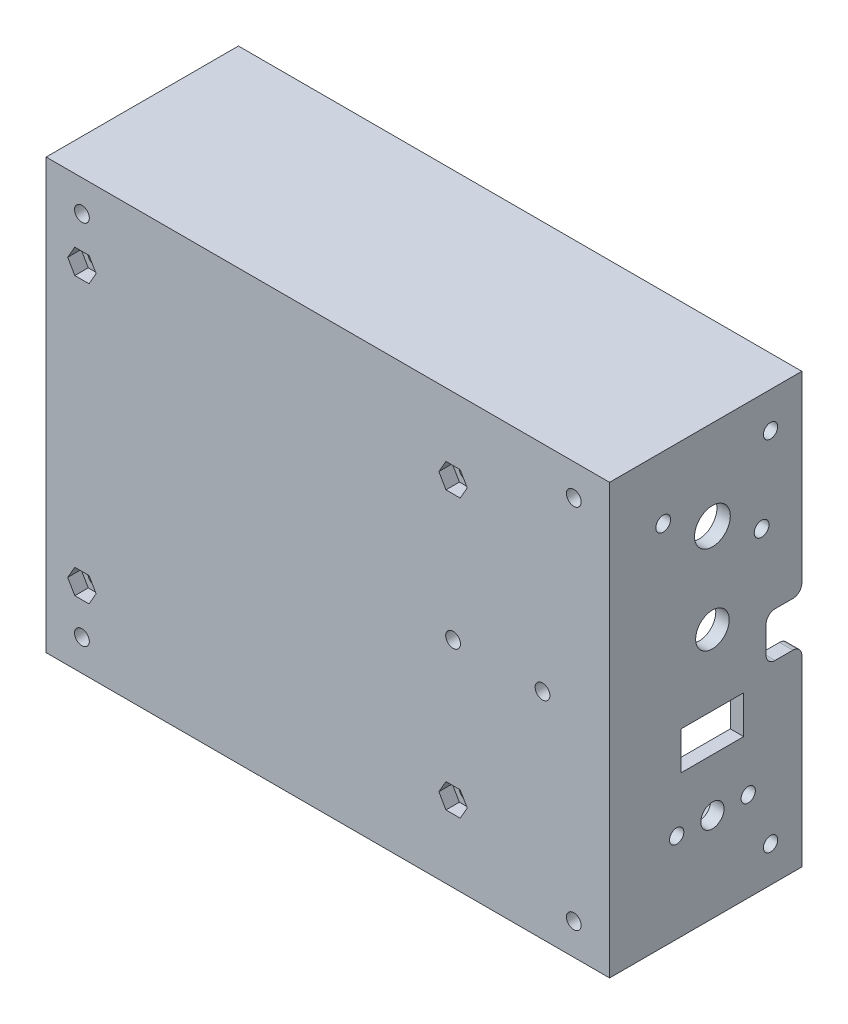
SolidWorks part; units mm, degrees
ref_plane "Front Plane" through (0, 0, 0) normal (0, 0, 1) x (1, 0, 0)
ref_plane "Top Plane" through (0, 0, 0) normal (0, 1, 0) x (1, 0, 0)
ref_plane "Right Plane" through (0, 0, 0) normal (1, 0, 0) x (0, 0, -1)
sketch "Sketch1" plane through (0, 0, 0) normal (0, 0, 1) x (1, 0, 0)
  line L1 (-60, -45) -> (60, -45)
  line L2 (-60, -45) -> (-60, 45)
  line L3 (-60, 45) -> (60, 45)
  line L4 (60, -45) -> (60, 45)
  line L5 (-60, -45) -> (60, 45) construction
  line L6 (-60, 45) -> (60, -45) construction
  line L7 (-55, -31) -> (28, -31)
  line L8 (-55, -31) -> (-55, 31)
  line L9 (-55, 31) -> (28, 31)
  line L10 (28, -31) -> (28, 31)
  line L11 (-55, -31) -> (28, 31) construction
  line L12 (-55, 31) -> (28, -31) construction
  circle A0 centre (-55, 31) radius 1.65
  circle A1 centre (28, 31) radius 1.65
  circle A2 centre (28, -31) radius 1.65
  circle A3 centre (-55, -31) radius 1.65
  circle A4 centre (-55, 41) radius 1.65
  circle A5 centre (55, 41) radius 1.65
  circle A6 centre (55, -41) radius 1.65
  circle A7 centre (-55, -41) radius 1.65
  point P0 (0, 0)
  point P6 (-13.5, 0)
  dimension "D7" = 3.3
  dimension "D8" = 4
  dimension "D9" = 5
  dimension "D10" = 5
  dimension "D11" = 4
  dimension "D12" = 3.3
  dimension "D13" = 5
  dimension "D14" = 4
  dimension "D15" = 4
  dimension "D16" = 5
  dimension "D1" = 90
  dimension "D2" = 120
  dimension "D3" = 62
  dimension "D4" = 83
  dimension "D5" = 14
  dimension "D6" = 5
extrude "Boss-Extrude2" add sketch "Sketch1" along normal blind 4 contours L1 L4 L3 L2 A3 L8 A0 L9 A1 L10 A2 L7 | A3 L7 A2 L10 A1 L9 A0 L8 region at (-58.5, 0, 0) region at (-13.5, 0, 0)
sketch "Sketch2" plane through (0, 0, 4) normal (0, 0, 1) x (1, 0, 0)
  line L1 (60, -45) -> (-60, -45)
  line L2 (60, -45) -> (60, 45)
  line L3 (60, 45) -> (-60, 45)
  line L4 (-60, -45) -> (-60, 45)
  line L5 (60, -45) -> (-60, 45) construction
  line L6 (60, 45) -> (-60, -45) construction
  line L7 (63, -48) -> (-63, -48)
  line L8 (63, -48) -> (63, 48)
  line L9 (63, 48) -> (-63, 48)
  line L10 (-63, -48) -> (-63, 48)
  line L11 (63, -48) -> (-63, 48) construction
  line L12 (63, 48) -> (-63, -48) construction
  point P0 (0, 0)
  point P7 (0, 0)
  dimension "D1" = 3
  dimension "D2" = 3
extrude "Boss-Extrude3" add sketch "Sketch2" against normal blind 43
sketch "Sketch3" plane through (-63, 0, 0) normal (-1, 0, 0) x (0, 0, 1)
  line L0 (-39, 48) -> (-39, -48) construction
  line L1 (-39, 48) -> (4, 48) construction
  line L2 (-39, -48) -> (4, -48) construction
  circle A0 centre (-32, -40) radius 1.6
  circle A1 centre (-32, 40) radius 1.6
  dimension "D1" = 3.2
  dimension "D2" = 7
  dimension "D3" = 8
  dimension "D4" = 8
  dimension "D5" = 7
  dimension "D6" = 3.2
extrude "Cut-Extrude1" cut sketch "Sketch3" against normal up to surface (126 mm away) up to face at (63, 0, -17.5)
sketch "Sketch4" plane through (63, 0, 0) normal (1, 0, 0) x (0, 0, -1)
  line L0 (39, -48) -> (39, 48) construction
  line L1 (39, 5) -> (31, 5)
  line L2 (39, 5) -> (39, -5)
  line L3 (39, -5) -> (31, -5)
  line L4 (31, 5) -> (31, -5)
  line L5 (39, -48) -> (-4, -48) construction
  line L6 (39, 48) -> (-4, 48) construction
  line L9 (12, -16.25) -> (26, -16.25)
  line L10 (12, -16.25) -> (12, -7.75)
  line L11 (12, -7.75) -> (26, -7.75)
  line L12 (26, -16.25) -> (26, -7.75)
  line L13 (12, -16.25) -> (26, -7.75) construction
  line L14 (12, -7.75) -> (26, -16.25) construction
  circle A1 centre (19, 8) radius 3.75
  point P8 (19, -12)
  dimension "D4" = 7.5
  dimension "D5" = 8.5
  dimension "D6" = 20
  dimension "D7" = 14
  dimension "D8" = 40
  dimension "D9" = 20
  dimension "D1" = 8
  dimension "D2" = 10
  dimension "D3" = 43
  dimension "D10" = 20
extrude "Cut-Extrude3" cut sketch "Sketch4" against normal blind 10
sketch "Sketch5" plane through (63, 0, 0) normal (1, 0, 0) x (0, 0, -1)
  line L0 (39, 5) -> (39, 48) construction
  line L1 (39, 48) -> (-4, 48) construction
  circle A0 centre (19, 28) radius 4
  dimension "D1" = 8
  dimension "D2" = 20
  dimension "D3" = 20
extrude "Cut-Extrude4" cut sketch "Sketch5" against normal blind 10
sketch "Sketch6" plane through (63, 0, 0) normal (1, 0, 0) x (0, 0, -1)
  line L0 (27, -28) -> (11, -28)
  line L1 (39, -48) -> (39, -5) construction
  line L3 (39, -48) -> (-4, -48) construction
  line L4 (-4, -48) -> (-4, 48) construction
  circle A0 centre (19, -28) radius 2.6
  circle A1 centre (11, -28) radius 1.6
  circle A2 centre (27, -28) radius 1.6
  point P3 (19, -28)
  dimension "D4" = 3.2
  dimension "D5" = 5.2
  dimension "D2" = 20
  dimension "D1" = 16
  dimension "D3" = 20
extrude "Cut-Extrude5" cut sketch "Sketch6" against normal blind 10 contours L0 A0 | A0 | A1 | A2 region at (63, -29.1035, -19)
sketch "Sketch8" plane through (0, 0, 0) normal (0, 0, -1) x (-1, 0, 0)
  line L0 (-60, 5) -> (-60, -5) construction
  circle A0 centre (-48, 0) radius 1.65
  circle A1 centre (-28, 0) radius 1.65
  circle A2 centre (-28, 31) radius 1.65 construction
  dimension "D1" = 3.3
  dimension "D2" = 3.3
  dimension "D3" = 20
  dimension "D4" = 31
  dimension "D5" = 31
  dimension "D6" = 12
extrude "Cut-Extrude6" cut sketch "Sketch8" against normal blind 10
sketch "Sketch9" plane through (0, 0, 0) normal (0, 0, -1) x (-1, 0, 0)
  line L0 (60, -45) -> (-60, -45) construction
  line L1 (-46.4123, 2.75) -> (-49.5877, 2.75)
  line L2 (-49.5877, 2.75) -> (-51.1754, 0)
  line L3 (-51.1754, 0) -> (-49.5877, -2.75)
  line L4 (-49.5877, -2.75) -> (-46.4123, -2.75)
  line L5 (-46.4123, -2.75) -> (-44.8246, 0)
  line L6 (-44.8246, 0) -> (-46.4123, 2.75)
  line L7 (-26.4123, 2.75) -> (-29.5877, 2.75)
  line L8 (-29.5877, 2.75) -> (-31.1754, 0)
  line L9 (-31.1754, 0) -> (-29.5877, -2.75)
  line L10 (-29.5877, -2.75) -> (-26.4123, -2.75)
  line L11 (-26.4123, -2.75) -> (-24.8246, 0)
  line L12 (-24.8246, 0) -> (-26.4123, 2.75)
  line L13 (-45.2576, 4.75) -> (-50.7424, 4.75)
  line L14 (-50.7424, 4.75) -> (-53.4848, 0)
  line L15 (-53.4848, 0) -> (-50.7424, -4.75)
  line L16 (-50.7424, -4.75) -> (-45.2576, -4.75)
  line L17 (-45.2576, -4.75) -> (-42.5152, 0)
  line L18 (-42.5152, 0) -> (-45.2576, 4.75)
  line L19 (-25.2576, 4.75) -> (-30.7424, 4.75)
  line L20 (-30.7424, 4.75) -> (-33.4848, 0)
  line L21 (-33.4848, 0) -> (-30.7424, -4.75)
  line L22 (-30.7424, -4.75) -> (-25.2576, -4.75)
  line L23 (-25.2576, -4.75) -> (-22.5152, 0)
  line L24 (-22.5152, 0) -> (-25.2576, 4.75)
  line L25 (60, -45) -> (-60, -45) construction
  line L26 (-51.8246, 41) -> (-53.4123, 43.75)
  line L27 (-53.4123, 43.75) -> (-56.5877, 43.75)
  line L28 (-56.5877, 43.75) -> (-58.1754, 41)
  line L29 (-58.1754, 41) -> (-56.5877, 38.25)
  line L30 (-56.5877, 38.25) -> (-53.4123, 38.25)
  line L31 (-53.4123, 38.25) -> (-51.8246, 41)
  line L32 (-50.6699, 41) -> (-52.8349, 44.75)
  line L33 (-52.8349, 44.75) -> (-57.1651, 44.75)
  line L34 (-57.1651, 44.75) -> (-59.3301, 41)
  line L35 (-59.3301, 41) -> (-57.1651, 37.25)
  line L36 (-57.1651, 37.25) -> (-52.8349, 37.25)
  line L37 (-52.8349, 37.25) -> (-50.6699, 41)
  line L38 (58.1754, 41) -> (56.5877, 43.75)
  line L39 (56.5877, 43.75) -> (53.4123, 43.75)
  line L40 (53.4123, 43.75) -> (51.8246, 41)
  line L41 (51.8246, 41) -> (53.4123, 38.25)
  line L42 (53.4123, 38.25) -> (56.5877, 38.25)
  line L43 (56.5877, 38.25) -> (58.1754, 41)
  line L44 (52.8349, 44.75) -> (50.6699, 41)
  line L45 (50.6699, 41) -> (52.8349, 37.25)
  line L46 (52.8349, 37.25) -> (57.1651, 37.25)
  line L47 (57.1651, 37.25) -> (59.3301, 41)
  line L48 (59.3301, 41) -> (57.1651, 44.75)
  line L49 (57.1651, 44.75) -> (52.8349, 44.75)
  line L50 (53.4123, -38.25) -> (51.8246, -41)
  line L51 (51.8246, -41) -> (53.4123, -43.75)
  line L52 (53.4123, -43.75) -> (56.5877, -43.75)
  line L53 (56.5877, -43.75) -> (58.1754, -41)
  line L54 (58.1754, -41) -> (56.5877, -38.25)
  line L55 (56.5877, -38.25) -> (53.4123, -38.25)
  line L56 (50.6699, -41) -> (52.8349, -44.75)
  line L57 (52.8349, -44.75) -> (57.1651, -44.75)
  line L58 (57.1651, -44.75) -> (59.3301, -41)
  line L59 (59.3301, -41) -> (57.1651, -37.25)
  line L60 (57.1651, -37.25) -> (52.8349, -37.25)
  line L61 (52.8349, -37.25) -> (50.6699, -41)
  line L62 (-53.4123, -38.25) -> (-56.5877, -38.25)
  line L63 (-56.5877, -38.25) -> (-58.1754, -41)
  line L64 (-58.1754, -41) -> (-56.5877, -43.75)
  line L65 (-56.5877, -43.75) -> (-53.4123, -43.75)
  line L66 (-53.4123, -43.75) -> (-51.8246, -41)
  line L67 (-51.8246, -41) -> (-53.4123, -38.25)
  line L68 (-52.8349, -37.25) -> (-57.1651, -37.25)
  line L69 (-57.1651, -37.25) -> (-59.3301, -41)
  line L70 (-59.3301, -41) -> (-57.1651, -44.75)
  line L71 (-57.1651, -44.75) -> (-52.8349, -44.75)
  line L72 (-52.8349, -44.75) -> (-50.6699, -41)
  line L73 (-50.6699, -41) -> (-52.8349, -37.25)
  circle A0 centre (-48, 0) radius 2.75 construction
  circle A1 centre (-28, 0) radius 2.75 construction
  circle A2 centre (-48, 0) radius 4.75 construction
  circle A3 centre (-28, 0) radius 4.75 construction
  circle A4 centre (-55, 41) radius 2.75 construction
  circle A5 centre (-55, 41) radius 3.75 construction
  circle A6 centre (55, 41) radius 2.75 construction
  circle A7 centre (55, 41) radius 3.75 construction
  circle A8 centre (55, -41) radius 2.75 construction
  circle A9 centre (55, -41) radius 3.75 construction
  circle A10 centre (-55, -41) radius 2.75 construction
  circle A11 centre (-55, -41) radius 3.75 construction
  dimension "D1" = 5.5
  dimension "D2" = 2
  dimension "D3" = 5.5
  dimension "D4" = 1
extrude "Boss-Extrude4" add sketch "Sketch9" along normal blind 3
sketch "Sketch10" plane through (0, 0, 4) normal (0, 0, 1) x (1, 0, 0)
  line L0 (63, 48) -> (-63, 48) construction
  line L1 (-51.8246, 31) -> (-53.4123, 33.75)
  line L2 (-53.4123, 33.75) -> (-56.5877, 33.75)
  line L3 (-56.5877, 33.75) -> (-58.1754, 31)
  line L4 (-58.1754, 31) -> (-56.5877, 28.25)
  line L5 (-56.5877, 28.25) -> (-53.4123, 28.25)
  line L6 (-53.4123, 28.25) -> (-51.8246, 31)
  line L7 (31.1754, 31) -> (29.5877, 33.75)
  line L8 (29.5877, 33.75) -> (26.4123, 33.75)
  line L9 (26.4123, 33.75) -> (24.8246, 31)
  line L10 (24.8246, 31) -> (26.4123, 28.25)
  line L11 (26.4123, 28.25) -> (29.5877, 28.25)
  line L12 (29.5877, 28.25) -> (31.1754, 31)
  line L25 (-51.8246, -31) -> (-53.4123, -28.25)
  line L26 (-53.4123, -28.25) -> (-56.5877, -28.25)
  line L27 (-56.5877, -28.25) -> (-58.1754, -31)
  line L28 (-58.1754, -31) -> (-56.5877, -33.75)
  line L29 (-56.5877, -33.75) -> (-53.4123, -33.75)
  line L30 (-53.4123, -33.75) -> (-51.8246, -31)
  line L31 (31.1754, -31) -> (29.5877, -28.25)
  line L32 (29.5877, -28.25) -> (26.4123, -28.25)
  line L33 (26.4123, -28.25) -> (24.8246, -31)
  line L34 (24.8246, -31) -> (26.4123, -33.75)
  line L35 (26.4123, -33.75) -> (29.5877, -33.75)
  line L36 (29.5877, -33.75) -> (31.1754, -31)
  circle A0 centre (-55, 31) radius 2.75 construction
  circle A1 centre (28, 31) radius 2.75 construction
  circle A4 centre (-55, -31) radius 2.75 construction
  circle A5 centre (28, -31) radius 2.75 construction
  dimension "D2" = 5.5
fillet "Fillet1" radius 2 4 edges at (61.5, 5, -31) (61.5, -5, -31) (61.5, -5, -39) (61.5, 5, -39)
extrude "Cut-Extrude8" cut sketch "Sketch10" against normal blind 3
sketch "Sketch12" plane through (0, 0, 0) normal (0, 0, -1) x (-1, 0, 0)
  circle A0 centre (-28, 31) radius 1.65
  circle A1 centre (55, 31) radius 1.65
  circle A2 centre (55, -31) radius 1.65
  circle A3 centre (-28, -31) radius 1.65
  circle A4 centre (-28, -31) radius 4
  circle A5 centre (55, -31) radius 4
  circle A6 centre (55, 31) radius 4
  circle A7 centre (-28, 31) radius 4
  dimension "D1" = 8
extrude "Boss-Extrude11" add sketch "Sketch12" along normal blind 5
sketch "Sketch13" plane through (60, 0, 0) normal (-1, 0, 0) x (0, 0, 1)
  line L1 (-25, 22) -> (-13, 22)
  line L2 (-25, 22) -> (-25, 34)
  line L3 (-25, 34) -> (-13, 34)
  line L4 (-13, 22) -> (-13, 34)
  line L5 (-25, 22) -> (-13, 34) construction
  line L6 (-25, 34) -> (-13, 22) construction
  line L7 (-35, 18) -> (-3, 18)
  line L8 (-35, 18) -> (-35, 38)
  line L9 (-35, 38) -> (-3, 38)
  line L10 (-3, 18) -> (-3, 38)
  line L11 (-35, 18) -> (-3, 38) construction
  line L12 (-35, 38) -> (-3, 18) construction
  point P0 (-19, 28)
  point P6 (-19, 28)
  dimension "D1" = 12
  dimension "D2" = 12
  dimension "D3" = 20
  dimension "D4" = 10
extrude "Boss-Extrude12" add sketch "Sketch13" along normal blind 2
chamfer "Chamfer1" distance 2 angle 45 2 edges at (60, 28, -3) (60, 28, -35)
sketch "Sketch14" plane through (58, 0, 0) normal (-1, 0, 0) x (0, 0, 1)
  line L0 (-3, 18) -> (-3, 38) construction
  line L1 (-35, 38) -> (-35, 18) construction
  line L2 (-35, 18) -> (-3, 18) construction
  line L5 (-3, 38) -> (-35, 38) construction
  circle A0 centre (-30, 22) radius 1.65
  circle A1 centre (-8, 34) radius 1.65
  dimension "D1" = 3.3
  dimension "D2" = 3.3
  dimension "D3" = 5
  dimension "D4" = 5
  dimension "D5" = 4
  dimension "D6" = 4
extrude "Cut-Extrude9" cut sketch "Sketch14" against normal blind 12
sketch "Sketch15" plane through (58, 0, 0) normal (-1, 0, 0) x (0, 0, 1)
  line L0 (-25, 34) -> (-25, 22) construction
  line L1 (-37, 38) -> (-28, 38)
  line L2 (-37, 38) -> (-37, 26)
  line L3 (-37, 26) -> (-28, 26)
  line L4 (-28, 38) -> (-28, 26)
  line L5 (-1, 18) -> (-10, 18)
  line L6 (-1, 18) -> (-1, 30)
  line L7 (-1, 30) -> (-10, 30)
  line L8 (-10, 18) -> (-10, 30)
  line L9 (-13, 22) -> (-13, 34) construction
  line L10 (-37, 18) -> (-37, 38) construction
  line L11 (-1, 38) -> (-1, 18) construction
  circle A0 centre (-30, 22) radius 1.65 construction
  circle A1 centre (-8, 34) radius 1.65 construction
  point P18 (0, 0)
  point P21 (0, 0)
  dimension "D1" = 4
  dimension "D2" = 3
  dimension "D3" = 3
  dimension "D4" = 4
extrude "Cut-Extrude10" cut sketch "Sketch15" against normal up to surface (2 mm away) up to face at (60, -28, -28.6)
chamfer "Chamfer3" distance 5 angle 45 1 edges at (59, 38, -28)
chamfer "Chamfer4" distance 5 angle 45 1 edges at (59, 18, -10)
chamfer "Chamfer5" distance 2 angle 45 1 edges at (60, 26.5, -10)
